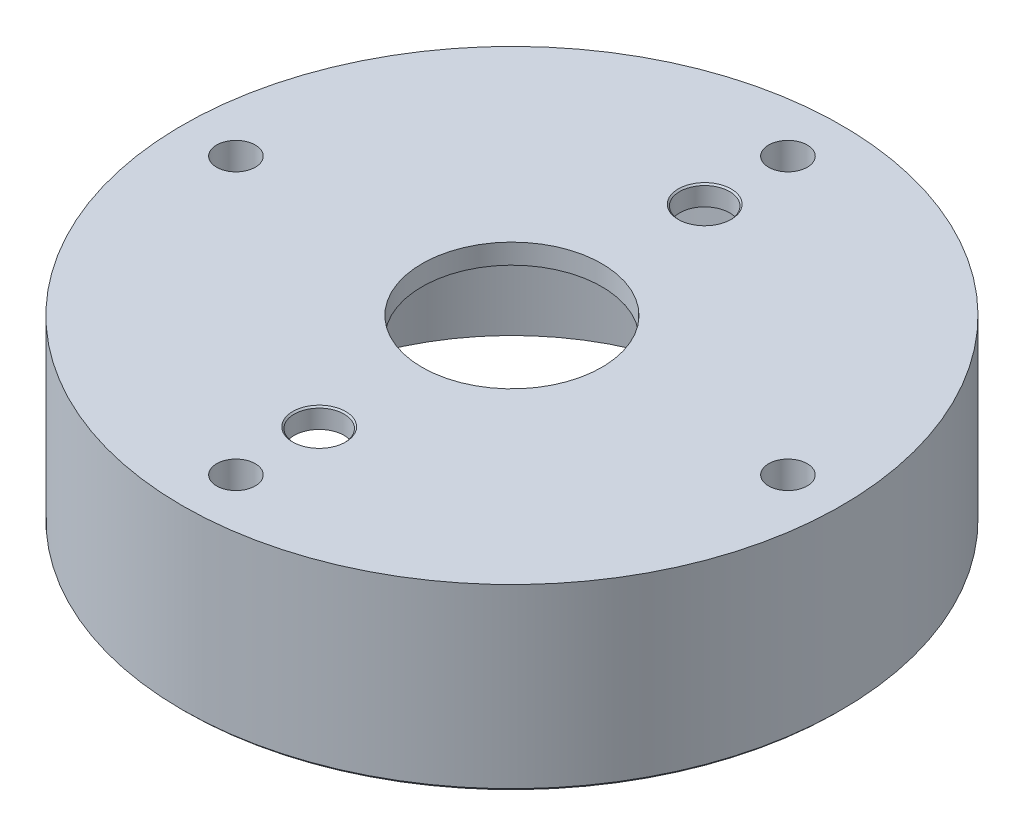
SolidWorks part; units mm, degrees
ref_plane "Front Plane" through (0, 0, 0) normal (0, 0, 1) x (1, 0, 0)
ref_plane "Top Plane" through (0, 0, 0) normal (0, 1, 0) x (1, 0, 0)
ref_plane "Right Plane" through (0, 0, 0) normal (1, 0, 0) x (0, 0, -1)
sketch "Sketch1" plane through (0, 0, 0) normal (0, 1, 0) x (1, 0, 0)
  circle A0 centre (0, 0) radius 11.5
  circle A1 centre (0, 0) radius 16.5
  dimension "D1" = 5
  dimension "D2" = 33
extrude "Boss-Extrude1" add sketch "Sketch1" along normal blind 8
sketch "Sketch2" plane through (0, 8, 0) normal (0, 1, 0) x (1, 0, 0)
  circle A0 centre (0, 0) radius 16.5
extrude "Boss-Extrude2" add sketch "Sketch2" along normal blind 1
sketch "Sketch3" plane through (0, 9, 0) normal (0, 1, 0) x (1, 0, 0)
  line L0 (0, 13) -> (0, 9.65)
  line L1 (0, -11.45) -> (0, -9.65)
  line L10 (0, 9.65) -> (0, 0)
  line L11 (0, 0) -> (0, -9.65)
  circle A0 centre (0, 0) radius 4.5
  circle A4 centre (0, 9.65) radius 1.25
  circle A5 centre (0, -9.65) radius 1.25
  dimension "D1" = 9
  dimension "D8" = 2.5
  dimension "D9" = 1.8
  dimension "D10" = 2.5
  dimension "D2" = 9.65
  dimension "D3" = 9.65
extrude "Cut-Extrude1" cut sketch "Sketch3" against normal blind 9.65 contours A0 | A4 | A5 | A0 | A4 | A5 region at (0.5305, 9, -9.65) region at (0.5305, 9, 9.65) region at (1.9099, 9, 0)
scale "Scale1" scale about centroid uniform scaling yes scale factor 1.666667
chamfer "Chamfer2" distance 0.125 angle 45 2 edges at (0, 11.7879, -14) (0, 11.7879, 18.1667)
chamfer "Chamfer4" distance 0.25 angle 45 1 edges at (0, -3.2121, 27.5)
sketch "Sketch4" plane through (0, 11.7879, 0) normal (0, 1, 0) x (1, 0, 0)
  circle A0 centre (23.03, 0) radius 1.6125
  circle A1 centre (0, 23.03) radius 1.6125
  circle A2 centre (0, -23.03) radius 1.6125
  circle A3 centre (-23.03, 0) radius 1.6125
  point P11 (0, 0)
  dimension "D2" = 3.225
  dimension "D1" = 4
extrude "Cut-Extrude2" cut sketch "Sketch4" against normal through all
